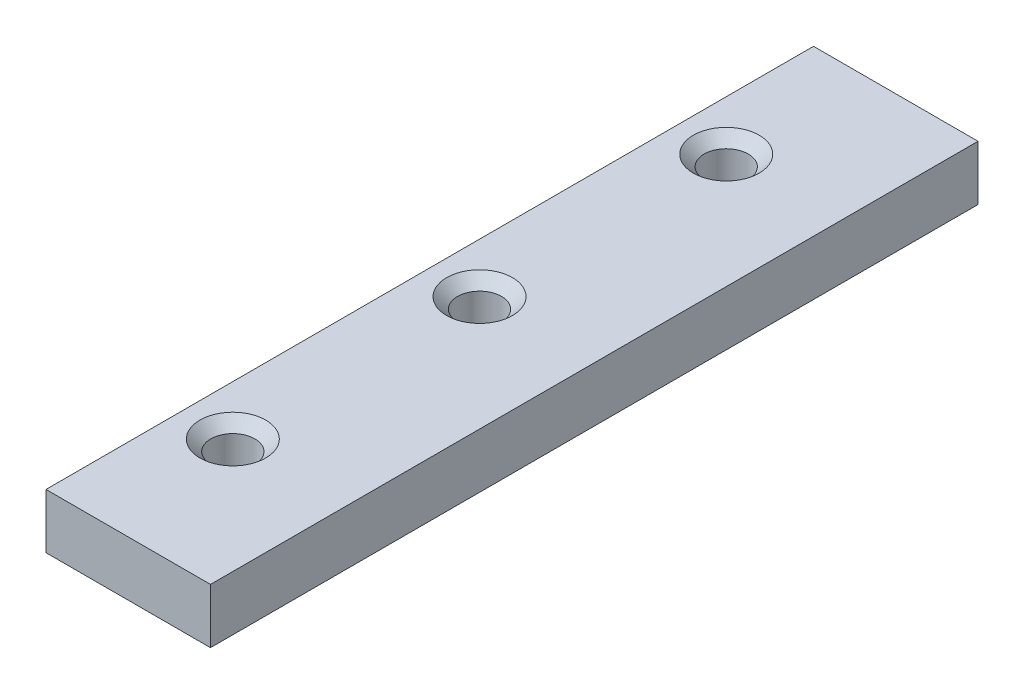
SolidWorks part; units mm, degrees
material "6061 Alloy"
ref_plane "Front Plane" through (0, 0, 0) normal (0, 0, 1) x (1, 0, 0)
ref_plane "Top Plane" through (0, 0, 0) normal (0, 1, 0) x (1, 0, 0)
ref_plane "Right Plane" through (0, 0, 0) normal (1, 0, 0) x (0, 0, -1)
sketch "Sketch1" plane through (0, 0, 0) normal (0, 1, 0) x (1, 0, 0)
  line L1 (0, 0) -> (-19.05, 0)
  line L2 (0, 0) -> (0, 88.9)
  line L3 (0, 88.9) -> (-19.05, 88.9)
  line L4 (-19.05, 0) -> (-19.05, 88.9)
  dimension "D1" = 88.9
  dimension "D2" = 19.05
extrude "Boss-Extrude1" add sketch "Sketch1" along normal blind 6.35
hole_wizard "1/4-20 Tapped Hole1" positions "Sketch2" profile "Sketch3" tap size "1/4-20" standard "ANSI Inch" end condition through all
sketch "Sketch2" plane through (0, 6.35, 0) normal (0, 1, 0) x (1, 0, 0)
  line L0 (-19.05, 0) -> (0, 0) construction
  line L1 (0, 88.9) -> (-19.05, 88.9) construction
  point P0 (-13.2844, 15.875)
  point P2 (-13.2844, 44.45)
  point P4 (-13.2844, 73.025)
  dimension "D1" = 15.875
  dimension "D2" = 15.875
  dimension "D3" = 44.45
sketch "Sketch3" plane through (-13.2844, 6.35, -15.875) normal (1, 0, 0) x (0, 0, 1)
  line L0 (0, 0) -> (0, 6.35)
  line L1 (0, 6.35) -> (2.5527, 6.35)
  line L2 (2.5527, 6.35) -> (2.5527, 1.2573)
  line L3 (2.5527, 1.2573) -> (3.81, 0)
  line L5 (3.81, 0) -> (0, 0)
  line L6 (-2.5527, 1.2573) -> (-3.81, 0) construction
  line L11 (0, -6.35) -> (0, 107.95) construction
  dimension "Thru Tap Drill Dia." = 5.1054
  dimension "Thru Tap Drill Depth" = 6.35
  dimension "Near C'Sink Dia." = 7.62
  dimension "Near C'Sink Angle" = 90
cosmetic thread "Hole Thread1"
cosmetic thread "Hole Thread2"
cosmetic thread "Hole Thread3"
